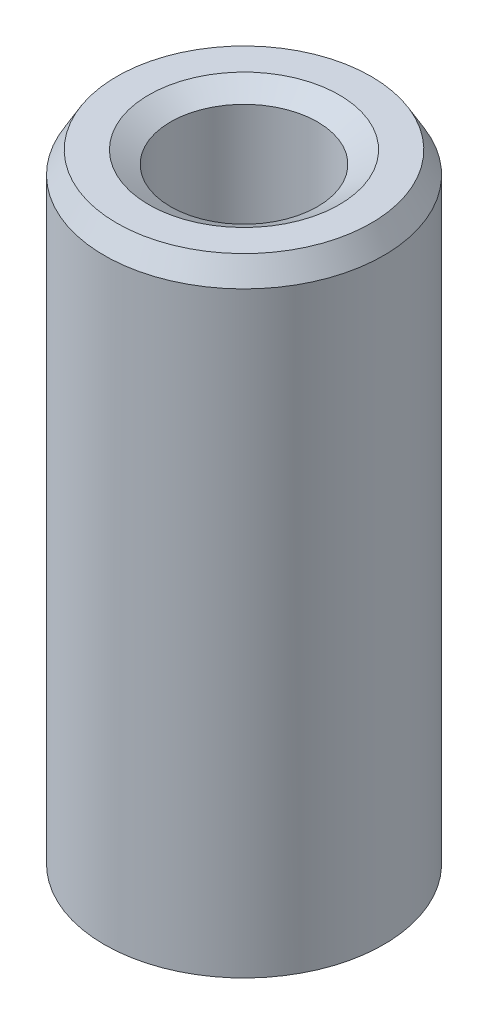
SolidWorks part; units mm, degrees
ref_plane "Front Plane" through (0, 0, 0) normal (0, 0, 1) x (1, 0, 0)
ref_plane "Top Plane" through (0, 0, 0) normal (0, 1, 0) x (1, 0, 0)
ref_plane "Right Plane" through (0, 0, 0) normal (1, 0, 0) x (0, 0, -1)
sketch "Sketch1" plane through (0, 0, 0) normal (0, 1, 0) x (1, 0, 0)
  circle A0 centre (0, 0) radius 25
  dimension "SLEEVE_OD" = 50
extrude "Boss-Extrude1" add sketch "Sketch1" along normal blind 112.9298
sketch "Sketch2" plane through (0, 0, 0) normal (0, 1, 0) x (1, 0, 0)
  circle A0 centre (0, 0) radius 13.1475
  dimension "BORE_D" = 26.295
extrude "Cut-Extrude1" cut sketch "Sketch2" along normal through all
chamfer "Chamfer1" distance 3.8885 angle 30 4 edges at (0, 112.9298, 13.1475) (0, 0, 13.1475) (0, 0, 25) (0, 112.9298, 25) first distance on face at (0, 112.9298, 13.1475) first distance on face at (0, 0, 13.1475) first distance on face at (0, 112.9298, 25)
